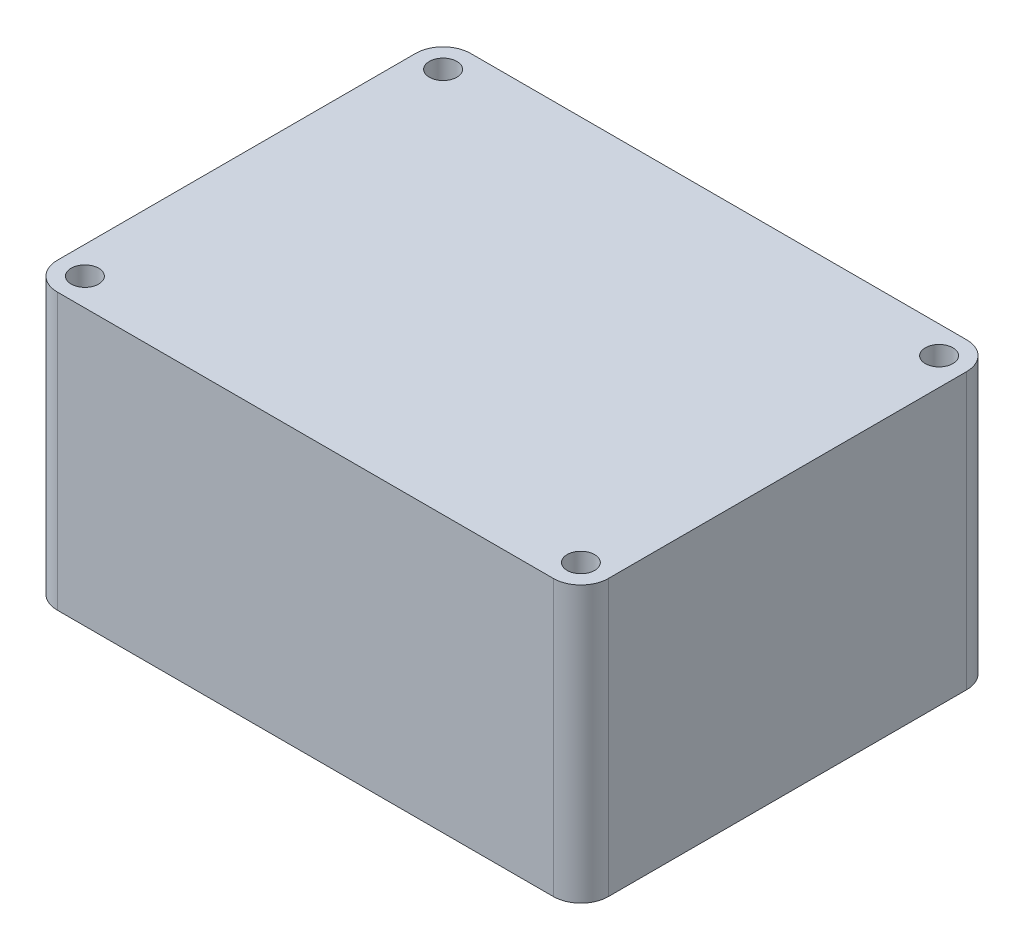
SolidWorks part; units mm, degrees
ref_plane "Alzado" through (0, 0, 0) normal (0, 0, 1) x (1, 0, 0)
ref_plane "Planta" through (0, 0, 0) normal (0, 1, 0) x (1, 0, 0)
ref_plane "Vista lateral" through (0, 0, 0) normal (1, 0, 0) x (0, 0, -1)
sketch "Croquis1" plane through (0, 0, 0) normal (0, 1, 0) x (1, 0, 0)
  line L0 (0, 75) -> (0, -75) construction
  line L1 (-100, 75) -> (100, 75)
  line L2 (-100, 75) -> (-100, -75)
  line L3 (-100, -75) -> (100, -75)
  line L4 (100, 75) -> (100, -75)
  dimension "D1" = 200
  dimension "D2" = 150
extrude "Saliente-Extruir1" add sketch "Croquis1" along normal blind 100
fillet "Redondeo1" radius 10 4 edges at (-100, 50, -75) (100, 50, -75) (100, 50, 75) (-100, 50, 75)
sketch "Croquis2" plane through (0, 100, 0) normal (0, 1, 0) x (1, 0, 0)
  circle A0 centre (-90, 65) radius 5
  dimension "D1" = 10
extrude "Cortar-Extruir1" cut sketch "Croquis2" against normal through all
mirror "Simetría1" about plane through (0, 0, 0) normal (0, 0, 1) of "Cortar-Extruir1" second plane through (0, 0, 0) second plane normal (1, 0, 0)
equation "\"Width\" = 200.0"
equation "\"Depth\" = 150.0"
equation "\"Height\" = 100.0"
equation "\"D1@Croquis1\"=\"Width\""
equation "\"D2@Croquis1\"=\"Depth\""
equation "\"D1@Saliente-Extruir1\"=\"Height\""
